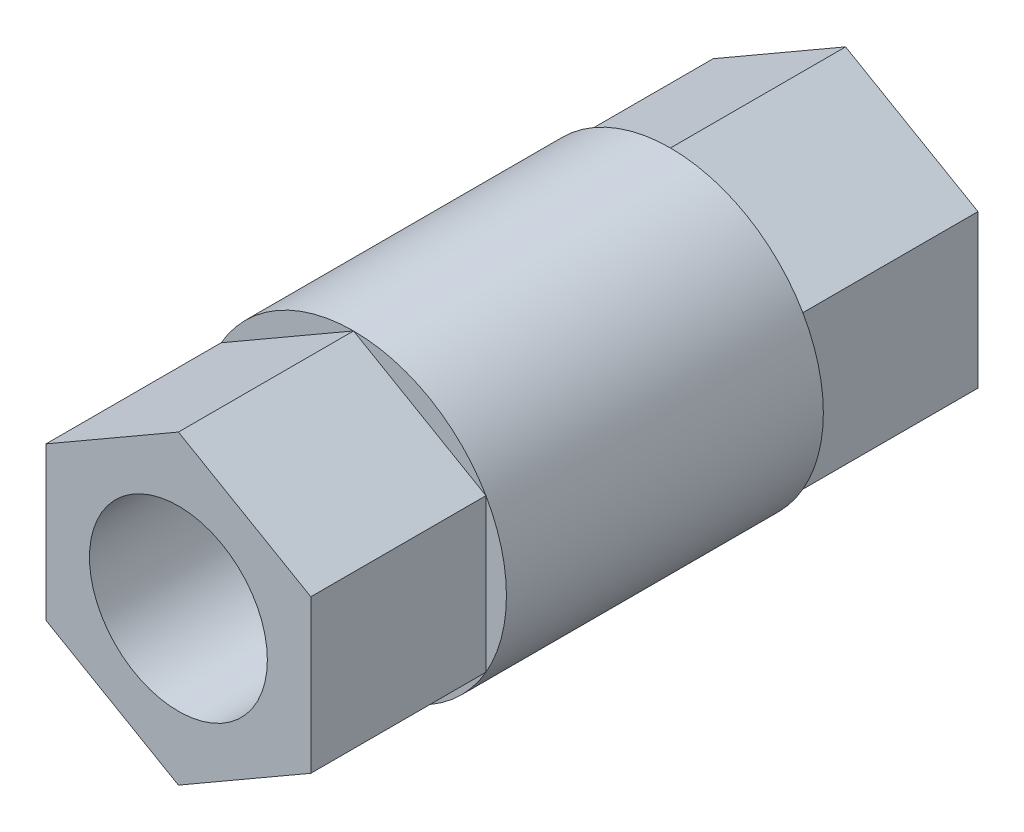
SolidWorks part; units mm, degrees
ref_plane "Front Plane" through (0, 0, 0) normal (0, 0, 1) x (1, 0, 0)
ref_plane "Top Plane" through (0, 0, 0) normal (0, 1, 0) x (1, 0, 0)
ref_plane "Right Plane" through (0, 0, 0) normal (1, 0, 0) x (0, 0, -1)
sketch "Sketch1" plane through (0, 0, 0) normal (0, 0, 1) x (1, 0, 0)
  line L1 (0, -11) -> (9.5263, -5.5)
  line L2 (9.5263, -5.5) -> (9.5263, 5.5)
  line L3 (9.5263, 5.5) -> (0, 11)
  line L4 (0, 11) -> (-9.5263, 5.5)
  line L5 (-9.5263, 5.5) -> (-9.5263, -5.5)
  line L6 (-9.5263, -5.5) -> (0, -11)
  circle A0 centre (0, 0) radius 11
  circle A1 centre (0, 0) radius 9.5263 construction
  circle A2 centre (0, 0) radius 6.4
  dimension "D1" = 22
  dimension "D2" = 12.8
extrude "Boss-Extrude1" add sketch "Sketch1" along normal mid plane 22.8 contours L4 A0 | L5 A0 | L5 L6 L1 L2 L3 L4 | L3 A0 | L2 A0 | L1 A0 | L6 A0 region at (-4.6176, -7.998, 0) region at (-5.0596, -8.7636, 0) region at (5.0596, -8.7636, 0) region at (10.1193, 0, 0) region at (-10.1193, 0, 0) region at (5.0596, 8.7636, 0) region at (-5.0596, 8.7636, 0)
extrude "Boss-Extrude2" add sketch "Sketch1<3>" along normal mid plane 48 contours L5 L6 L1 L2 L3 L4 A2 region at (-4.6176, -7.998, 0)
sketch "Sketch1<3>" plane through (0, 0, 0) normal (0, 0, 1) x (1, 0, 0) same geometry as "Sketch1"
